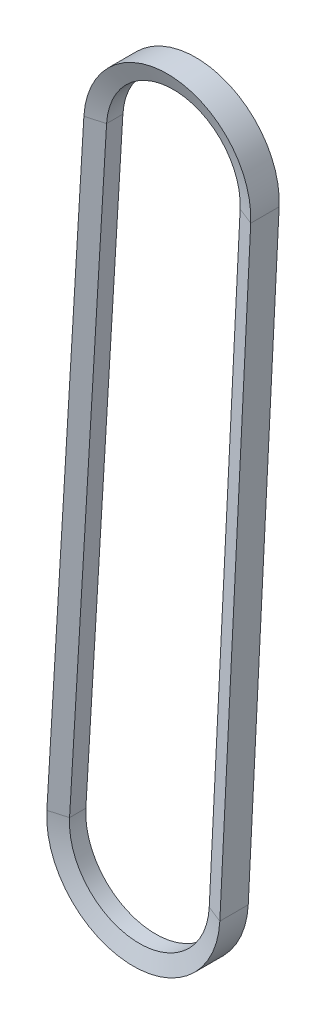
SolidWorks part; units mm, degrees
ref_plane "Front Plane" through (0, 0, 0) normal (0, 0, 1) x (1, 0, 0)
ref_plane "Top Plane" through (0, 0, 0) normal (0, 1, 0) x (1, 0, 0)
ref_plane "Right Plane" through (0, 0, 0) normal (1, 0, 0) x (0, 0, -1)
sketch "Sketch2" plane through (0, 0, 0) normal (0, 0, 1) x (1, 0, 0)
  line L0 (0, 0) -> (1, 0) construction
  line L1 (0, 0) -> (0, 1) construction
  line L2 (27.9652, -1.3947) -> (17.6044, -209.134)
  line L3 (-40.3591, -205.9565) -> (-27.9501, 1.6705)
  arc A0 (-27.9501, 1.6705) -> (27.9652, -1.3947) centre (0, 0) cw
  arc A1 (17.6044, -209.134) -> (-40.3591, -205.9565) centre (-11.3852, -207.6882) cw
ref_plane "Plane4" through (27.9652, -1.3947, 0) normal (-0.0498, -0.9988, 0) x (-0.9988, 0.0498, 0)
sketch "Sketch3" plane through (27.9652, -1.3947, 0) normal (-0.0498, -0.9988, 0) x (-0.9988, 0.0498, 0)
  line L0 (0, 4.7625) -> (0, -4.7625)
  line L1 (0, 4.7625) -> (5.588, 2.7286)
  line L2 (5.588, 2.7286) -> (5.588, -2.7286)
  line L3 (5.588, -2.7286) -> (0, -4.7625)
  line L4 (0, 0) -> (5.588, 0) construction
  point P2 (0, 0)
  dimension "D1" = 9.525
  dimension "D2" = 5.588
  dimension "D3" = 40
sweep "Sweep1" add profiles "Sketch3" path "Sketch2"
